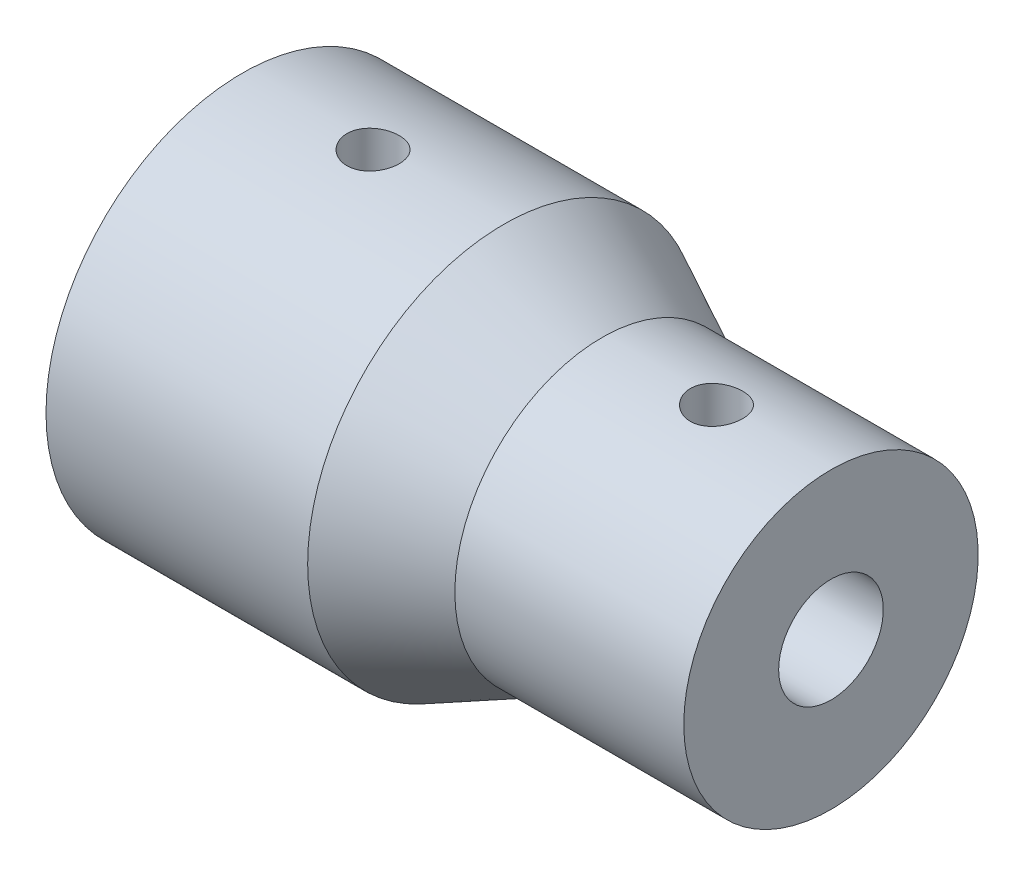
SolidWorks part; units mm, degrees
ref_plane "Front Plane" through (0, 0, 0) normal (0, 0, 1) x (1, 0, 0)
ref_plane "Top Plane" through (0, 0, 0) normal (0, 1, 0) x (1, 0, 0)
ref_plane "Right Plane" through (0, 0, 0) normal (1, 0, 0) x (0, 0, -1)
sketch "Sketch1" plane through (0, 0, 0) normal (0, 1, 0) x (1, 0, 0)
  line L0 (0, 0) -> (50114.9151, 0) construction
  line L1 (0, -1002.2983) -> (0, 0) construction
  line L2 (-10.16, 3.3655) -> (0, 3.3655)
  line L3 (0, 7.62) -> (3.81, 5.715)
  line L4 (-10.16, 3.3655) -> (-10.16, 7.62)
  line L5 (-10.16, 7.62) -> (0, 7.62)
  line L8 (12.7, 5.715) -> (12.7, 2.032)
  line L9 (0, 3.3655) -> (0, 50114.9151) construction
  line L10 (0, 3.3655) -> (2.54, 2.032)
  line L11 (2.54, 2.032) -> (12.7, 2.032)
  line L12 (3.81, 5.715) -> (12.7, 5.715)
  line L13 (0.4092, 3.3655) -> (50000.4092, 3.3655) construction
  line L14 (0, 7.62) -> (50000, 7.62) construction
  dimension "D1" = 4.064
  dimension "D2" = 6.731
  dimension "D3" = 2.54
  dimension "D4" = 15.24
  dimension "D5" = 11.43
  dimension "D6" = 22.86
  dimension "D7" = 10.16
  dimension "D8" = 3.81
revolve "Revolve1" add sketch "Sketch1" angle 360 about L0
sketch "Sketch2" plane through (0, 0, 0) normal (0, 1, 0) x (1, 0, 0)
  line L0 (0, 0) -> (50000, 0) construction
  line L1 (0, 7.62) -> (-10.16, 7.62) construction
  line L2 (-5.08, 7.62) -> (-5.08, 0) construction
  line L3 (8.255, 5.715) -> (8.255, 0) construction
  line L4 (12.7, 5.715) -> (3.81, 5.715) construction
  circle A0 centre (-5.08, 0) radius 1.016
  circle A1 centre (8.255, 0) radius 1.016
  dimension "D1" = 2.032
  dimension "D2" = 2.032
extrude "Cut-Extrude1" cut sketch "Sketch2" along normal through all
pattern_circular "CirPattern1" count 2 every 90 about axis through (-10.16, 0, 0) along (-1, 0, 0) of "Cut-Extrude1"
equation "\"D2@Sketch2\"=\"D1@Sketch2\""
